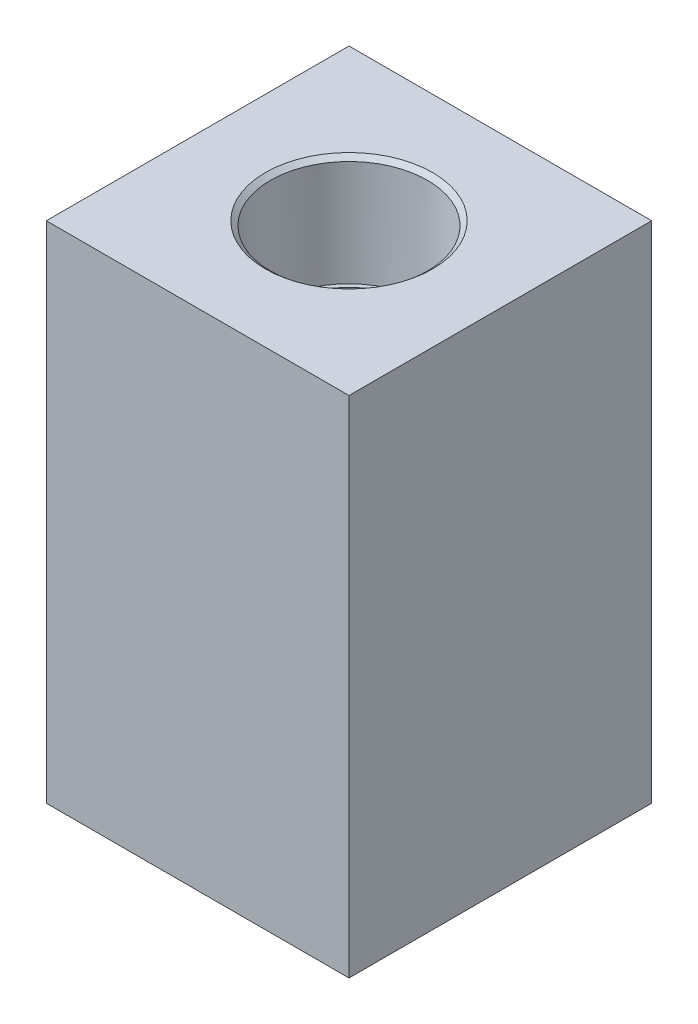
SolidWorks part; units mm, degrees
material "AISI 316 Stainless Steel Sheet (SS)"
ref_plane "前视基准面" through (0, 0, 0) normal (0, 0, 1) x (1, 0, 0)
ref_plane "上视基准面" through (0, 0, 0) normal (0, 1, 0) x (1, 0, 0)
ref_plane "右视基准面" through (0, 0, 0) normal (1, 0, 0) x (0, 0, -1)
other "Configuration Table"
sketch "草图1" plane through (0, 0, 0) normal (0, 1, 0) x (1, 0, 0)
  line L1 (-19.05, 19.05) -> (19.05, 19.05)
  line L2 (-19.05, 19.05) -> (-19.05, -19.05)
  line L3 (-19.05, -19.05) -> (19.05, -19.05)
  line L4 (19.05, 19.05) -> (19.05, -19.05)
  line L5 (-19.05, 19.05) -> (19.05, -19.05) construction
  line L6 (-19.05, -19.05) -> (19.05, 19.05) construction
  point P0 (0, 0)
  dimension "D1" = 38.1
  dimension "D2" = 38.1
extrude "凸台-拉伸1" add sketch "草图1" along normal blind 63.5 contours L1 L4 L3 L2
hole_wizard "1/2 NPT Tapped Hole2" positions "Sketch1" profile "Sketch2" size "1/2" standard "ANSI Inch"
sketch "Sketch1" plane through (0, 63.5, 0) normal (0, 1, 0) x (1, 0, 0)
  point P0 (0, 0)
sketch "Sketch2" plane through (0, 63.5, 0) normal (1, 0, 0) x (0, 0, 1)
  line L0 (0, 0) -> (0, 28.0045)
  line L1 (8.9281, 22.64) -> (0, 28.0045)
  line L2 (-8.9281, 22.64) -> (0, 28.0045) construction
  line L3 (8.9281, 22.64) -> (8.9281, 13.57)
  line L4 (8.9281, 13.57) -> (9.479, 13.57)
  line L5 (9.479, 13.57) -> (9.886, 0.5328)
  line L6 (9.886, 0.5328) -> (10.521, 0)
  line L7 (10.521, 0) -> (0, 0)
  line L8 (0, -6.35) -> (0, 107.95) construction
  line L9 (-9.886, 0.5328) -> (-10.521, 0) construction
  line L11 (-8.9281, 13.57) -> (-9.479, 13.57) construction
  line L12 (-9.479, 13.57) -> (-9.886, 0.5328) construction
  dimension "Tap Drill Dia." = 17.8562
  dimension "Tap Drill Depth" = 22.64
  dimension "Thread Dia." = 19.772
  dimension "Thread Angle" = 3.576
  dimension "Thread Depth" = 13.57
  dimension "C'Sink Dia." = 21.042
  dimension "C'Sink Angle" = 100
  dimension "Drill Angle" = 118
cosmetic thread "Hole Thread1" parameters "D1"=13.57, "D2"=21.3359
hole_wizard "1/2 NPT Tapped Hole1" positions "Sketch3" profile "Sketch4" size "1/2" standard "ANSI Inch"
sketch "Sketch3" plane through (0, 0, 0) normal (0, -1, 0) x (1, 0, 0)
  point P0 (0.4289, -0.9864)
sketch "Sketch4" plane through (0.4289, 0, -0.9864) normal (1, 0, 0) x (0, 0, -1)
  line L0 (0, 0) -> (0, 28.0045)
  line L1 (8.9281, 22.64) -> (0, 28.0045)
  line L2 (-8.9281, 22.64) -> (0, 28.0045) construction
  line L3 (8.9281, 22.64) -> (8.9281, 13.57)
  line L4 (8.9281, 13.57) -> (9.479, 13.57)
  line L5 (9.479, 13.57) -> (9.886, 0.5328)
  line L6 (9.886, 0.5328) -> (10.521, 0)
  line L7 (10.521, 0) -> (0, 0)
  line L8 (0, -6.35) -> (0, 107.95) construction
  line L9 (-9.886, 0.5328) -> (-10.521, 0) construction
  line L11 (-8.9281, 13.57) -> (-9.479, 13.57) construction
  line L12 (-9.479, 13.57) -> (-9.886, 0.5328) construction
  dimension "Tap Drill Dia." = 17.8562
  dimension "Tap Drill Depth" = 22.64
  dimension "Thread Dia." = 19.772
  dimension "Thread Angle" = 3.576
  dimension "Thread Depth" = 13.57
  dimension "C'Sink Dia." = 21.042
  dimension "C'Sink Angle" = 100
  dimension "Drill Angle" = 118
cosmetic thread "Hole Thread2" parameters "D1"=13.57, "D2"=21.3352
sketch "Sketch5" plane through (0, 63.5, 0) normal (0, 1, 0) x (1, 0, 0)
  circle A0 centre (0, 0) radius 5.588
  dimension "D1" = 11.176
extrude "Cut-Extrude1" cut sketch "Sketch5" against normal through all
ref_axis "Flow_axis" through (0, 24.0006, 0) along (0, 1, 0)
